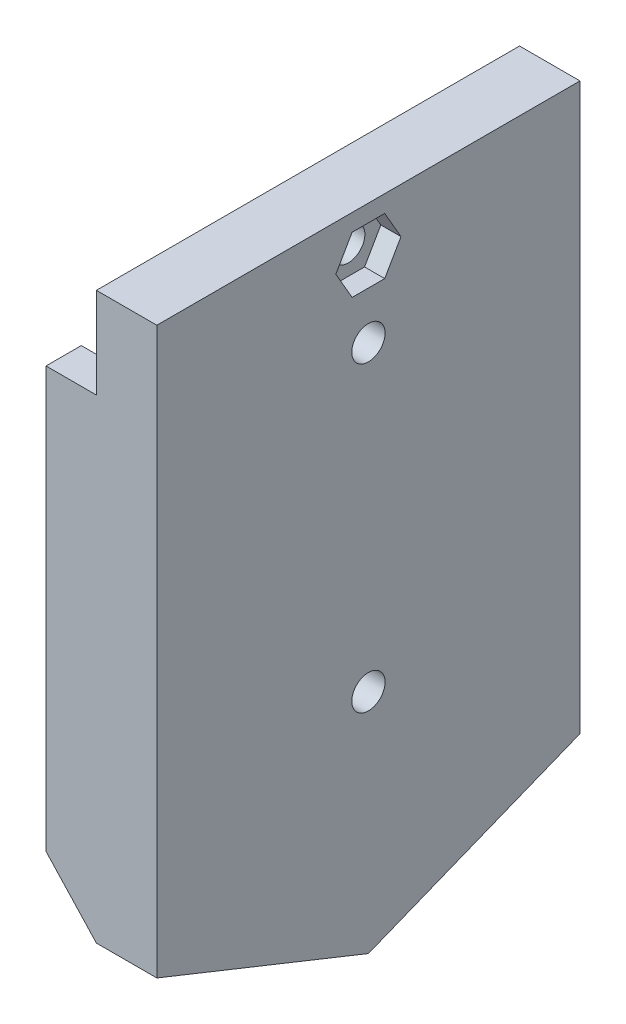
SolidWorks part; units mm, degrees
ref_plane "Plano frontal" through (0, 0, 0) normal (0, 0, 1) x (1, 0, 0)
ref_plane "Plano superior" through (0, 0, 0) normal (0, 1, 0) x (1, 0, 0)
ref_plane "Plano direito" through (0, 0, 0) normal (1, 0, 0) x (0, 0, -1)
sketch "Esboço1" plane through (0, 0, 0) normal (0, 0, 1) x (1, 0, 0)
  line L0 (0, 0) -> (6, 0) construction
  line L1 (0, 32.5) -> (0, -32.5)
  line L6 (6, -32.5) -> (6, 32.5)
  line L7 (6, -32.5) -> (0, -32.5)
  line L10 (6, 32.5) -> (0, 32.5)
  point P3 (0, 0)
  dimension "D3" = 6
  dimension "D4" = 65
extrude "Ressalto-extrusão1" add sketch "Esboço1" along normal mid plane 42
sketch "Esboço11" plane through (0, 0, 0) normal (-1, 0, 0) x (0, 0, 1)
  line L0 (-17.5, -9.5) -> (0, -16.5)
  line L1 (21, 32.5) -> (-21, 32.5) construction
  line L2 (-17.5, 23.5) -> (-17.5, -9.5)
  line L4 (17.5, 23.5) -> (17.5, -9.5)
  line L5 (-17.5, 23.5) -> (17.5, -9.5) construction
  line L6 (-17.5, -9.5) -> (17.5, 23.5) construction
  line L7 (0, -16.5) -> (17.5, -9.5)
  line L9 (-21, 23.5) -> (-17.5, 23.5)
  line L10 (21, 23.5) -> (21, -16.7163)
  line L11 (21, 32.5) -> (21, -32.5) construction
  line L12 (21, -16.7163) -> (0, -25.1163)
  line L13 (0, -25.1163) -> (-21, -16.7163)
  line L14 (-21, 32.5) -> (-21, -32.5) construction
  line L15 (-21, -16.7163) -> (-21, 23.5)
  line L17 (17.5, 23.5) -> (21, 23.5)
  point P0 (0, 7)
  dimension "D1" = 35
  dimension "D2" = 7
  dimension "D3" = 42
  dimension "D4" = 33
  dimension "D5" = 8
extrude "Ressalto-extrusão4" add sketch "Esboço11" along normal blind 5
sketch "Esboço12" plane through (-5, 0, 0) normal (-1, 0, 0) x (0, 0, 1)
  line L0 (-17.5, -9.5) -> (17.5, -9.5)
  line L1 (17.5, -9.5) -> (17.5, -16.5)
  line L2 (17.5, -16.5) -> (0, -23.5)
  line L3 (0, -23.5) -> (-17.5, -16.5)
  line L4 (-17.5, -16.5) -> (-17.5, -9.5)
  line L5 (-17.5, -9.5) -> (0, -16.5) construction
  dimension "D1" = 7
extrude "Corte-extrusão6" cut sketch "Esboço12" against normal up to surface (5 mm away) from offset 1 up to face at (0, 13.7222, 0) offset against normal yes
chamfer "Chanfro1" distance 6.4 angle 45 2 edges at (-4, -20, -8.75) (-4, -20, 8.75)
chamfer "Chanfro2" distance 6.4 angle 45 2 edges at (0, -20.9163, -10.5) (0, -20.9163, 10.5)
sketch "Esboço15" plane through (-5, 0, 0) normal (-1, 0, 0) x (0, 0, 1)
  circle A0 centre (0, 28) radius 1.65
  circle A1 centre (0, 20.5) radius 1.65
  circle A2 centre (0, -9.5) radius 1.65
  point P2 (17.5, -9.5)
  dimension "D1" = 37.5
  dimension "D2" = 3.3
  dimension "D3" = 30
  dimension "D4" = 0
extrude "Corte-extrusão7" cut sketch "Esboço15" against normal through all
sketch "Esboço16" plane through (6, 0, 0) normal (1, 0, 0) x (0, 0, -1)
  line L1 (3.2332, 28) -> (1.6166, 30.8)
  line L2 (1.6166, 30.8) -> (-1.6166, 30.8)
  line L3 (-1.6166, 30.8) -> (-3.2332, 28)
  line L4 (-3.2332, 28) -> (-1.6166, 25.2)
  line L5 (-1.6166, 25.2) -> (1.6166, 25.2)
  line L6 (1.6166, 25.2) -> (3.2332, 28)
  circle A0 centre (0, 28) radius 2.8 construction
  dimension "D1" = 5.6
extrude "Corte-extrusão8" cut sketch "Esboço16" against normal blind 2
sketch "Esboço17" plane through (0, 0, 0) normal (-1, 0, 0) x (0, 0, 1)
  circle A0 centre (0, 20.5) radius 3.5
  circle A1 centre (0, -9.5) radius 3.5
  dimension "D1" = 7
extrude "Corte-extrusão9" cut sketch "Esboço17" against normal blind 2.5
sketch "Esboço18" plane through (0, 0, 0) normal (-1, 0, 0) x (0, 0, 1)
  line L3 (21, -23.6093) -> (0, -32.0093)
  line L4 (21, -23.6093) -> (0, -32.0093)
  line L5 (0, -32.0093) -> (-21, -23.6093)
  line L6 (0, -32.0093) -> (-21, -23.6093)
  line L9 (-21, -23.6093) -> (-21, -32.5)
  line L10 (-21, -23.6093) -> (-21, -32.5)
  line L11 (-21, -32.5) -> (21, -32.5)
  line L12 (-21, -32.5) -> (21, -32.5)
  line L13 (21, -32.5) -> (21, -23.6093)
  line L14 (21, -32.5) -> (21, -23.6093)
  dimension "D1" = 0
extrude "Corte-extrusão10" cut sketch "Esboço18" against normal through all
